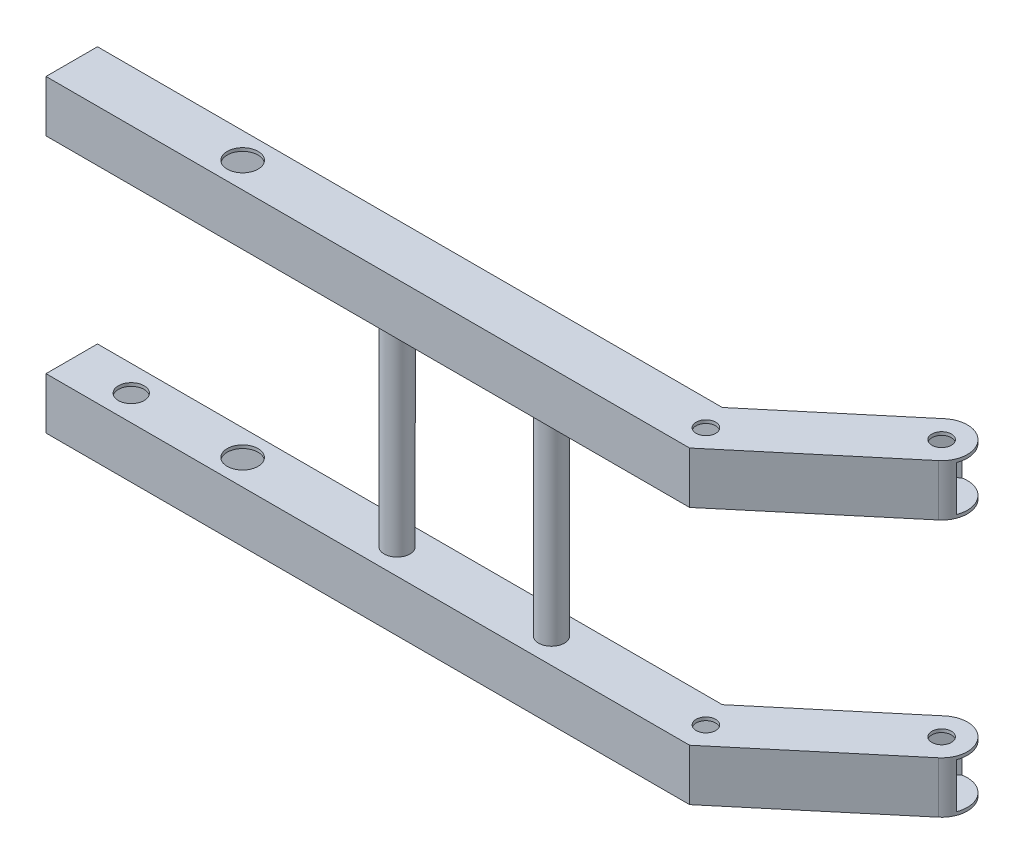
SolidWorks part; units mm, degrees
ref_plane "Front Plane" through (0, 0, 0) normal (0, 0, 1) x (1, 0, 0)
ref_plane "Top Plane" through (0, 0, 0) normal (0, 1, 0) x (1, 0, 0)
ref_plane "Right Plane" through (0, 0, 0) normal (1, 0, 0) x (0, 0, -1)
sketch "Sketch4" plane through (0, 0, 0) normal (0, 1, 0) x (1, 0, 0)
  line L0 (0, 0) -> (-254, 0) construction
  line L1 (0, 0) -> (91.1351, 76.4714) construction
  line L2 (-254, -12.7) -> (-254, 12.7)
  line L3 (4.6224, -12.7) -> (-4.6224, 12.7) construction
  line L4 (-254, 12.7) -> (-4.6224, 12.7)
  line L5 (99.2985, 66.7427) -> (82.9717, 86.2002)
  line L6 (82.9717, 86.2002) -> (-4.6224, 12.7)
  line L7 (-254, -12.7) -> (4.6224, -12.7)
  line L8 (4.6224, -12.7) -> (99.2985, 66.7427)
  circle A0 centre (0, 0) radius 4.826
  circle A1 centre (63.237, 53.0621) radius 4.826
  circle A3 centre (-228.6, 0) radius 7.62
  point P7 (-254, 0)
  point P10 (0, 0)
  point P13 (91.1351, 76.4714)
  dimension "D2" = 9.652
  dimension "D7" = 15.24
  dimension "D1" = 82.55
  dimension "D3" = 25.4
  dimension "D5" = 25.4
  dimension "D6" = 228.6
extrude "Boss-Extrude3" add sketch "Sketch4" along normal blind 152.4
sketch "Sketch5" plane through (-254, 0, 0) normal (-1, 0, 0) x (0, 0, 1)
  line L0 (0, 152.4) -> (0, 0) construction
  line L3 (-12.7, 152.4) -> (12.7, 152.4) construction
  line L6 (-12.7, 0) -> (12.7, 0) construction
  line L7 (11.1125, 128.5875) -> (-11.1125, 128.5875)
  line L8 (11.1125, 128.5875) -> (11.1125, 150.8125)
  line L9 (11.1125, 150.8125) -> (-11.1125, 150.8125)
  line L10 (-11.1125, 128.5875) -> (-11.1125, 150.8125)
  line L11 (11.1125, 128.5875) -> (-11.1125, 150.8125) construction
  line L12 (11.1125, 150.8125) -> (-11.1125, 128.5875) construction
  line L13 (-12.7, 127) -> (12.7, 127)
  line L14 (-12.7, 152.4) -> (-12.7, 0) construction
  line L15 (12.7, 152.4) -> (12.7, 0) construction
  line L16 (11.1125, 1.5875) -> (-11.1125, 1.5875)
  line L17 (11.1125, 1.5875) -> (11.1125, 23.8125)
  line L18 (11.1125, 23.8125) -> (-11.1125, 23.8125)
  line L19 (-11.1125, 1.5875) -> (-11.1125, 23.8125)
  line L20 (11.1125, 1.5875) -> (-11.1125, 23.8125) construction
  line L21 (11.1125, 23.8125) -> (-11.1125, 1.5875) construction
  line L22 (-12.7, 25.4) -> (12.7, 25.4)
  line L23 (-12.7, 25.4) -> (-12.7, 127)
  line L24 (12.7, 127) -> (12.7, 25.4)
  point P12 (0, 139.7)
  point P19 (0, 12.7)
  point P26 (0, 25.4)
  dimension "D1" = 1.5875
  dimension "D2" = 12.7
  dimension "D3" = 12.7
  dimension "D4" = 1.5875
  dimension "D5" = 12.7
  dimension "D6" = 12.7
extrude "Cut-Extrude2" cut sketch "Sketch5" against normal up to vertex (258.6224 mm away) up to point (4.6224, 152.4, 12.7)
sketch "Sketch6" plane through (91.1351, 0, -76.4714) normal (0.766, 0, -0.6428) x (-0.6428, 0, -0.766)
  line L0 (12.7, 127) -> (-12.7, 127)
  line L1 (12.7, 152.4) -> (12.7, 0) construction
  line L3 (0, 0) -> (0, 152.4) construction
  line L4 (-12.7, 0) -> (12.7, 0) construction
  line L5 (-12.7, 152.4) -> (12.7, 152.4) construction
  line L6 (-12.7, 152.4) -> (-12.7, 0) construction
  line L7 (-11.1125, 128.5875) -> (11.1125, 128.5875)
  line L8 (-11.1125, 128.5875) -> (-11.1125, 150.8125)
  line L9 (-11.1125, 150.8125) -> (11.1125, 150.8125)
  line L10 (11.1125, 128.5875) -> (11.1125, 150.8125)
  line L11 (-11.1125, 128.5875) -> (11.1125, 150.8125) construction
  line L12 (-11.1125, 150.8125) -> (11.1125, 128.5875) construction
  line L13 (12.7, 25.4) -> (-12.7, 25.4)
  line L14 (-11.1125, 1.5875) -> (11.1125, 1.5875)
  line L15 (-11.1125, 1.5875) -> (-11.1125, 23.8125)
  line L16 (-11.1125, 23.8125) -> (11.1125, 23.8125)
  line L17 (11.1125, 1.5875) -> (11.1125, 23.8125)
  line L18 (-11.1125, 1.5875) -> (11.1125, 23.8125) construction
  line L19 (-11.1125, 23.8125) -> (11.1125, 1.5875) construction
  line L20 (-12.7, 25.4) -> (-12.7, 127)
  line L21 (12.7, 127) -> (12.7, 25.4)
  point P5 (0, 127)
  point P12 (0, 139.7)
  point P18 (0, 25.4)
  point P19 (0, 12.7)
  dimension "D1" = 1.5875
  dimension "D2" = 12.7
  dimension "D3" = 12.7
  dimension "D4" = 1.5875
  dimension "D5" = 25.4
  dimension "D6" = 12.7
extrude "Cut-Extrude3" cut sketch "Sketch6" against normal up to vertex (123.5909 mm away) up to point (4.6224, 152.4, 12.7)
sketch "Sketch7" plane through (0, 152.4, 0) normal (0, 1, 0) x (1, 0, 0)
  line L0 (71.4004, 43.3334) -> (55.0736, 62.7909) construction
  line L1 (82.9717, 86.2002) -> (-4.6224, 12.7) construction
  line L2 (4.6224, -12.7) -> (99.2985, 66.7427) construction
  line L3 (55.0736, 62.7909) -> (14.2925, 190.3795)
  line L4 (14.2925, 190.3795) -> (153.8443, 116.5917)
  line L5 (153.8443, 116.5917) -> (141.5355, -3.4731)
  line L6 (141.5355, -3.4731) -> (71.4004, 43.3334)
  arc A0 (55.0736, 62.7909) -> (71.4004, 43.3334) centre (63.237, 53.0621) cw
  point P6 (63.237, 53.0621)
  point P7 (63.237, 53.0621)
extrude "Cut-Extrude4" cut sketch "Sketch7" against normal up to surface (152.4 mm away) up to face at (-54.2883, 0, -25.4905)
sketch "Sketch8" plane through (0, 127, 0) normal (0, -1, 0) x (1, 0, 0)
  line L0 (0, 0) -> (-228.6, 0) construction
  circle A0 centre (-76.2, 0) radius 6.35
  circle A1 centre (-152.4, 0) radius 6.35
  dimension "D3" = 12.7
  dimension "D1" = 76.2
  dimension "D2" = 76.2
extrude "Boss-Extrude4" add sketch "Sketch8" along normal up to surface (101.6 mm away) up to face at (-61.9662, 25.4, -19.0479)
sketch "Sketch9" plane through (-254, 0, 0) normal (-1, 0, 0) x (0, 0, 1)
  line L0 (-12.7, 152.4) -> (12.7, 152.4)
  line L1 (12.7, 152.4) -> (12.7, 127)
  line L2 (12.7, 127) -> (-12.7, 127)
  line L3 (-12.7, 152.4) -> (-12.7, 127) construction
  line L4 (12.7, 127) -> (-12.7, 127) construction
  line L5 (-12.7, 127) -> (-12.7, 152.4)
  line L6 (-11.1125, 150.8125) -> (11.1125, 150.8125)
  line L7 (11.1125, 150.8125) -> (11.1125, 128.5875)
  line L8 (11.1125, 128.5875) -> (-11.1125, 128.5875)
  line L9 (-11.1125, 128.5875) -> (-11.1125, 150.8125)
  line L10 (-12.7, 25.4) -> (12.7, 25.4)
  line L11 (12.7, 25.4) -> (12.7, 0)
  line L12 (12.7, 0) -> (-12.7, 0)
  line L13 (-12.7, 0) -> (-12.7, 25.4)
  line L14 (-11.1125, 23.8125) -> (11.1125, 23.8125)
  line L15 (11.1125, 23.8125) -> (11.1125, 1.5875)
  line L16 (11.1125, 1.5875) -> (-11.1125, 1.5875)
  line L17 (-11.1125, 1.5875) -> (-11.1125, 23.8125)
extrude "Boss-Extrude5" add sketch "Sketch9" along normal blind 58.928
sketch "Sketch11" plane through (0, 127, 0) normal (0, -1, 0) x (1, 0, 0)
  line L0 (-312.928, 0) -> (-228.6, 0) construction
  line L1 (-312.928, -12.7) -> (-312.928, 12.7) construction
  circle A0 centre (-271.0548, 0) radius 1.65
  circle A1 centre (-296.0548, 0) radius 1.65
  dimension "D2" = 3.3
  dimension "D1" = 25
extrude "Cut-Extrude6" cut sketch "Sketch11" against normal up to surface (1.5875 mm away) up to face at (0, 128.5875, -4.826)
sketch "Sketch12" plane through (0, 127, 0) normal (0, -1, 0) x (1, 0, 0)
  line L0 (-271.0548, 0) -> (-296.0548, 0) construction
  circle A0 centre (-283.5548, 0) radius 6.35
extrude "Cut-Extrude7" cut sketch "Sketch12" along normal up to surface (103.1875 mm away) up to face at (-228.6, 23.8125, 7.62)
